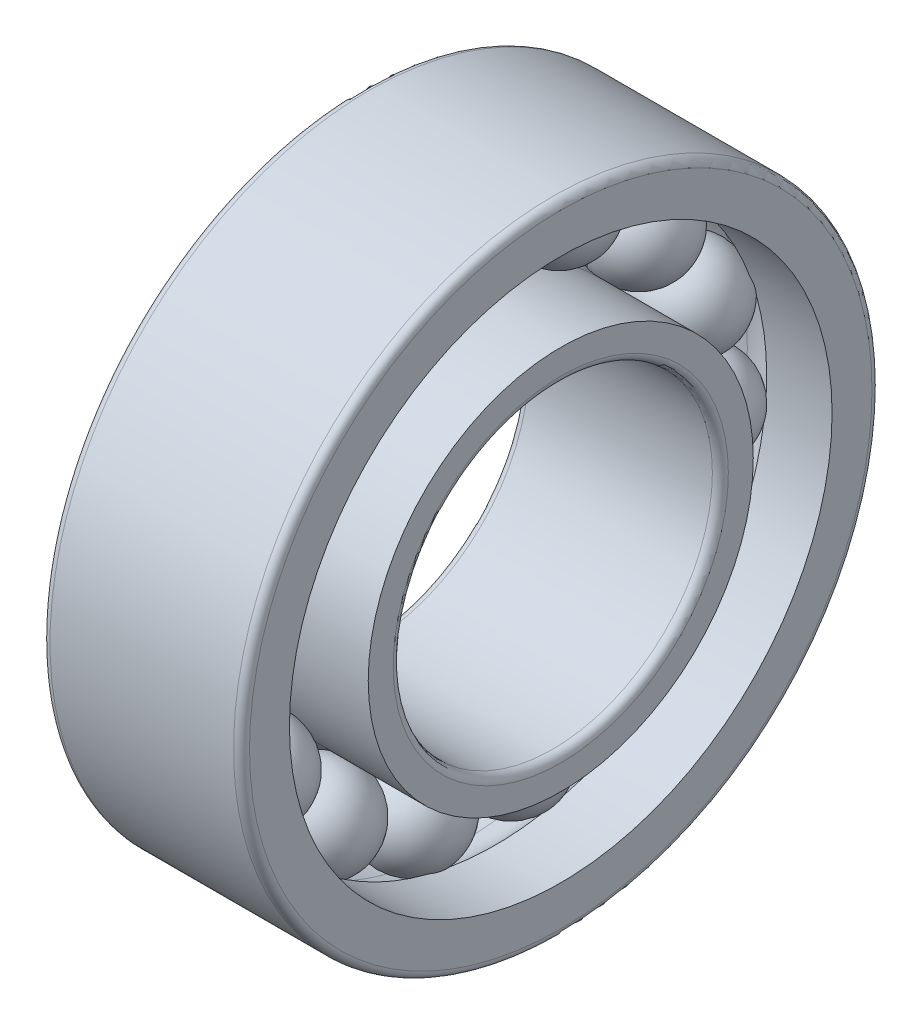
SolidWorks part; units mm, degrees
ref_plane "Plane1" through (0, 0, 0) normal (0, 0, 1) x (1, 0, 0)
ref_plane "Plane2" through (0, 0, 0) normal (0, 1, 0) x (1, 0, 0)
ref_plane "Plane3" through (0, 0, 0) normal (1, 0, 0) x (0, 0, -1)
other "Configuration Table"
sketch "Clipboard" plane through (0, 0, 0) normal (0, 0, 1) x (1, 0, 0)
  line L0 (-10, 0) -> (10, 0) construction
  line L1 (0, 0) -> (21.5988, -5.7874)
  line L2 (0, 0) -> (5.9991, -0.1047)
  line L3 (0, 0) -> (22.3573, 0.3902)
  line L4 (0, 0) -> (-22.3573, -0.3902)
sketch "CagSpiSke" plane through (0, 0, 0) normal (0, 0, 1) x (1, 0, 0)
  line L0 (0.3, 5.8) -> (0.3, 6.2)
  line L1 (0.3, 6.2) -> (-0.3, 6.2)
  line L2 (-0.3, 6.2) -> (-0.3, 5.8)
  line L3 (-0.3, 5.8) -> (0.3, 5.8)
  line L4 (-20.6375, 0) -> (20.6375, 0) construction
  line L5 (0, 0) -> (0, 23.7692) construction
revolve "CageSpine" add sketch "CagSpiSke" angle 0.001 about L4
ref_axis "Axis1" through (-50, 0, 0) along (1, 0, 0)
sketch "CagBalSke" plane through (0, 0, 0) normal (0, 0, 1) x (1, 0, 0)
  line L0 (-1.32, 6) -> (1.32, 6)
  line L1 (-1.905, 6) -> (1.905, 6) construction
  line L2 (-10, 0) -> (10, 0) construction
  line L3 (0, 0) -> (0, 24) construction
  arc A0 (1.32, 6) -> (-1.32, 6) centre (0, 6) cw
revolve "CageBall" [suppressed] add sketch "CagBalSke" angle 360 about L1 reverse direction yes
pattern_circular "CageBalls" [suppressed] count 15 every 24 about axis through (-50, 0, 0) along (1, 0, 0)
sketch "CagTrmODSke" plane through (0, 0, 0) normal (0, 0, 1) x (1, 0, 0)
  line L0 (1.321, 6.2) -> (1.321, 7.321)
  line L1 (1.321, 7.321) -> (-1.321, 7.321)
  line L2 (-1.321, 7.321) -> (-1.321, 6.2)
  line L3 (-1.321, 6.2) -> (1.321, 6.2)
  line L4 (-20.6375, 0) -> (20.6375, 0) construction
  line L5 (0, 0) -> (0, 25) construction
revolve "CageTrimOD" [suppressed] cut sketch "CagTrmODSke" angle 360 about L4 reverse direction yes
sketch "CagTrmIDSke" plane through (0, 0, 0) normal (0, 0, 1) x (1, 0, 0)
  line L0 (1.321, 4.681) -> (1.321, 5.8)
  line L1 (1.321, 5.8) -> (-1.321, 5.8)
  line L2 (-1.321, 5.8) -> (-1.321, 4.681)
  line L3 (-1.321, 4.681) -> (1.321, 4.681)
  line L4 (-20.6375, 0) -> (20.6375, 0) construction
  line L5 (0, 0) -> (0, 25) construction
revolve "CageTrimID" [suppressed] cut sketch "CagTrmIDSke" angle 360 about L4 reverse direction yes
sketch "BalSimSke" plane through (0, 0, 0) normal (0, 0, 1) x (1, 0, 0)
  line L0 (-10, 0) -> (10, 0) construction
  line L1 (-10, 6) -> (10, 6) construction
  line L2 (0, 0) -> (0, 23) construction
  circle A0 centre (0, 6) radius 1.2
revolve "BallsSimplified" [suppressed] add sketch "BalSimSke" angle 360 about L0
sketch "BalDetSke" plane through (0, 0, 0) normal (0, 0, 1) x (1, 0, 0)
  line L0 (-1.2, 6) -> (1.2, 6)
  line L1 (-1.905, 6) -> (1.905, 6) construction
  line L2 (0, 0) -> (0, 25) construction
  arc A0 (1.2, 6) -> (-1.2, 6) centre (0, 6) cw
revolve "BallDetailed" add sketch "BalDetSke" angle 360 about L1 reverse direction yes
sketch "InnRacSke" plane through (0, 0, 0) normal (0, 0, 1) x (1, 0, 0)
  line L0 (-0.8606, 5.2) -> (-2.5, 5.2)
  line L1 (-2.5, 5.2) -> (-2.5, 4.2)
  line L2 (-2.3, 4) -> (2.3, 4)
  line L3 (2.5, 4.2) -> (2.5, 4.825)
  line L4 (0, 4.825) -> (2.5, 4.825)
  line L5 (-20.6375, 0) -> (20.6375, 0) construction
  line L6 (0, 0) -> (0, 30) construction
  arc A0 (-2.5, 4.2) -> (-2.3, 4) centre (-2.3, 4.2) ccw
  arc A1 (2.3, 4) -> (2.5, 4.2) centre (2.3, 4.2) ccw
  arc A2 (0, 4.825) -> (-0.8606, 5.2) centre (0, 6) cw
revolve "InnerRace" add sketch "InnRacSke" angle 360 about L5 reverse direction yes
sketch "OutRacSke" plane through (0, 0, 0) normal (0, 0, 1) x (1, 0, 0)
  line L0 (0, 7.175) -> (-2.5, 7.175)
  line L1 (-2.5, 7.175) -> (-2.5, 7.8)
  line L2 (-2.3, 8) -> (2.3, 8)
  line L3 (2.5, 7.8) -> (2.5, 6.8)
  line L4 (2.5, 6.8) -> (0.8606, 6.8)
  line L5 (-20.6375, 0) -> (20.6375, 0) construction
  line L6 (0, 0) -> (0, 30) construction
  arc A0 (-2.5, 7.8) -> (-2.3, 8) centre (-2.3, 7.8) cw
  arc A1 (2.3, 8) -> (2.5, 7.8) centre (2.3, 7.8) cw
  arc A2 (0.8606, 6.8) -> (0, 7.175) centre (0, 6) ccw
revolve "OuterRace" add sketch "OutRacSke" angle 360 about L5 reverse direction yes
pattern_circular "BallsDetailed" count 15 every 24 about axis through (-50, 0, 0) along (1, 0, 0) of "BallDetailed"
equation "\"BallCLRad@Clipboard\" = ( \"OD@OutRacSke\" + \"ID@InnRacSke\" ) / 4"
equation "\"BallCLRad@BalSimSke\" = \"BallCLRad@Clipboard\""
equation "\"BallCLRad@BalDetSke\" = \"BallCLRad@Clipboard\""
equation "\"BallCLRad@InnRacSke\" = \"BallCLRad@Clipboard\""
equation "\"BallCLRad@OutRacSke\" = \"BallCLRad@Clipboard\""
equation "\"Ball_diameter@InnRacSke\" = \"Ball_diameter@BalDetSke\" - 0.05"
equation "\"Ball_diameter@OutRacSke\" = \"Ball_diameter@BalDetSke\" - 0.05"
equation "\"Ball_diameter@BalSimSke\" = \"Ball_diameter@BalDetSke\""
equation "\"Width@OutRacSke\" = \"Width@InnRacSke\""
equation "\"Fillet_radius@OutRacSke\" = \"Fillet_radius@InnRacSke\""
equation "\"Max_count@Clipboard\" = int( 3.14159265 / atn(( \"Ball_diameter@BalDetSke\" / 2) / sqr( \"BallCLRad@Clipboard\"  *  \"BallCLRad@Clipboard\" - ( \"Ball_diameter@BalDetSke\" / 2) *  ( \"Ball_diameter@BalDetSke\" / 2))))"
equation "\"Max_count@Clipboard\" = ((sgn( \"Max_count@Clipboard\" - \"Count@Clipboard\" )-1)*( \"Max_count@Clipboard\" - \"Count@Clipboard\" ))/-2+ \"Count@Clipboard\""
equation "\"Count@BallsDetailed\" = int( \"Show_count@Clipboard\" ) "
equation "\"Count@BallsDetailed\" = ((sgn( \"Count@BallsDetailed\" - \"Max_count@Clipboard\" )-1)*( \"Count@BallsDetailed\" - \"Max_count@Clipboard\" ))/-2+ \"Max_count@Clipboard\""
equation "\"Count@BallsDetailed\" = ((sgn( \"Count@BallsDetailed\" - \"Min_count@Clipboard\" )+1)*( \"Count@BallsDetailed\" - \"Min_count@Clipboard\"))/2 +\"Min_count@Clipboard\""
equation "\"Angle@BallsDetailed\" = 360.0 / \"Max_count@Clipboard\""
equation "\"BallCLRad@CagBalSke\" = \"BallCLRad@Clipboard\""
equation "\"Count@CageBalls\" = \"Count@BallsDetailed\""
equation "\"Angle@CageBalls\" = \"Angle@BallsDetailed\""
equation "\"Angle@CageSpine\" =  \"Angle@CageBalls\" * ( \"Count@CageBalls\" -1 + int( \"Count@CageBalls\" / \"Max_count@Clipboard\" ) )  + 0.001 -  int( \"Count@CageBalls\" / \"Max_count@Clipboard\" ) * 0.001"
equation "\"Angle@CageSpine\" =  \"Angle@CageSpine\" * int( \"Min_count@Clipboard\" / 2) + int(1 / \"Min_count@Clipboard\")  * 0.001"
equation "\"CageWallOD@CagBalSke\" =  \"Ball_diameter@BalDetSke\" * 1.1"
equation "\"Thickness@CagSpiSke\" =  \"Ball_diameter@BalDetSke\" * 0.25"
equation "\"OD@CagTrmODSke\" = \"BallCLRad@Clipboard\" * 2 + \"CageWallOD@CagBalSke\" + 0.002"
equation "\"ID@CagTrmODSke\" = \"BallCLRad@Clipboard\" * 2 + \"Ball_diameter@BalDetSke\" / 6"
equation "\"OD@CagTrmIDSke\" = \"BallCLRad@Clipboard\" * 2 - \"Ball_diameter@BalDetSke\" / 6"
equation "\"ID@CagTrmIDSke\" = \"BallCLRad@Clipboard\" * 2 - \"CageWallOD@CagBalSke\" + 0.002"
equation "\"OD@CagSpiSke\" = \"ID@CagTrmODSke\""
equation "\"ID@CagSpiSke\" = \"OD@CagTrmIDSke\""
equation "\"Width@CagTrmODSke\" = \"CageWallOD@CagBalSke\" + 0.002"
equation "\"Width@CagTrmIDSke\" = \"CageWallOD@CagBalSke\" + 0.002"
